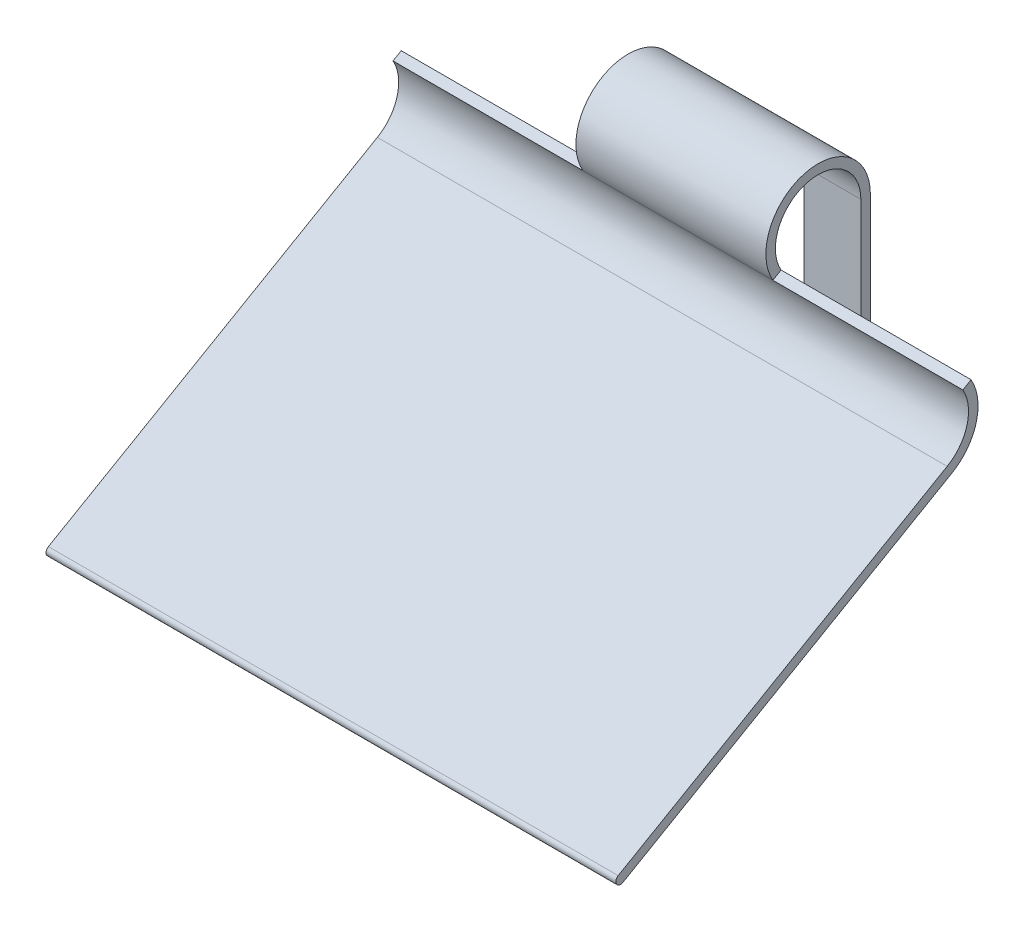
SolidWorks part; units mm, degrees
ref_plane "Front Plane" through (0, 0, 0) normal (1, 0, 0) x (0, 1, 0)
ref_plane "Top Plane" through (0, 0, 0) normal (0, 0, 1) x (0, 1, 0)
ref_plane "Right Plane" through (0, 0, 0) normal (0, 1, 0) x (-1, 0, 0)
sketch "Sketch1" plane through (0, 0, 0) normal (1, 0, 0) x (0, 1, 0)
  line L0 (0, 57.4277) -> (0, -57.4277) construction
  line L1 (0, 0) -> (-50.7985, 87.9856) construction
  line L2 (23.6985, -28.347) -> (-50.7985, -28.347) construction
  line L3 (23.6985, -29.617) -> (-50.7985, -29.617)
  line L4 (1.0999, 0.635) -> (-49.6987, 88.6206)
  line L5 (23.6985, -27.077) -> (-50.7985, -27.077)
  line L6 (-1.0999, -0.635) -> (-51.8984, 87.3506)
  line L7 (16.7135, -3.5487) -> (17.9835, -5.7484)
  arc A0 (0, 0) -> (17.3485, -4.6485) centre (10.9985, 6.35) ccw construction
  arc A1 (17.3485, -4.6485) -> (23.6985, -28.347) centre (23.6985, -15.647) cw construction
  arc A2 (16.7135, -3.5487) -> (23.6985, -29.617) centre (23.6985, -15.647) cw
  arc A3 (1.0999, 0.635) -> (16.7135, -3.5487) centre (10.9985, 6.35) ccw
  arc A4 (17.9835, -5.7484) -> (23.6985, -27.077) centre (23.6985, -15.647) cw
  arc A5 (-1.0999, -0.635) -> (17.9835, -5.7484) centre (10.9985, 6.35) ccw
  arc A6 (-50.7985, -29.617) -> (-50.7985, -27.077) centre (-50.7985, -28.347) cw
  arc A7 (-49.6987, 88.6206) -> (-51.8984, 87.3506) centre (-50.7985, 87.9856) ccw
  point P9 (17.9835, -5.7484)
  point P25 (0, 0)
  dimension "D3" = 12.7
  dimension "D4" = 12.7
  dimension "D1" = 87.9856
  dimension "D2" = 30
  dimension "D5" = 1.27
  dimension "D6" = 1.27
extrude "Boss-Extrude1" add sketch "Sketch1" along normal blind 76.2 and the other way blind 76.2 contours L4 A7 L6 A5 L7 A3 region at (0, -20.1663, 36.4228)
extrude "Boss-Extrude3" add sketch "Sketch1<5>" along normal blind 25.4 and the other way blind 25.4 contours A6 L3 A2 L7 A4 L5 region at (0, -13.55, -28.6772)
sketch "Sketch1<5>" plane through (0, 0, 0) normal (1, 0, 0) x (0, 1, 0) same geometry as "Sketch1"
sketch "Sketch5" plane through (0, 0, -29.617) normal (0, 0, -1) x (1, 0, 0)
  line L0 (0, 50.7985) -> (0, -23.6985) construction
  line L1 (-25.4, 50.7985) -> (25.4, 50.7985) construction
  line L2 (-25.4, -23.6985) -> (25.4, -23.6985) construction
  line L3 (10.16, 50.7985) -> (10.16, -23.6985)
  line L4 (-10.16, 50.7985) -> (-10.16, -23.6985)
  line L6 (10.16, -23.6985) -> (-10.16, -23.6985)
  line L7 (0, 50.7985) -> (0, 53.4982) construction
  line L8 (-10.16, 50.7985) -> (-10.16, 53.4982)
  line L9 (-10.16, 53.4982) -> (0, 53.4982)
  line L10 (0, 53.4982) -> (10.16, 53.4982)
  line L11 (10.16, 53.4982) -> (10.16, 50.7985)
  dimension "D1" = 10.16
  dimension "D2" = 10.16
extrude "Cut-Extrude2" cut sketch "Sketch5" against normal blind 3.81
